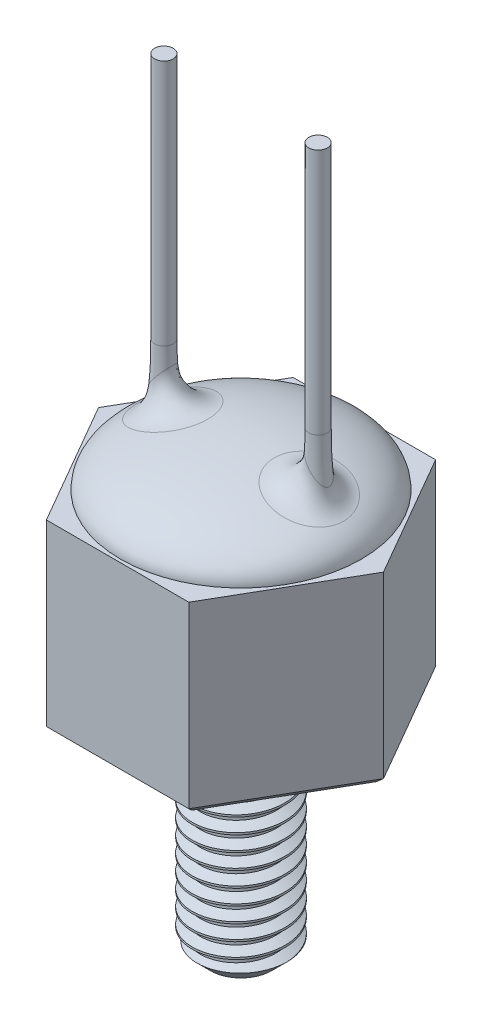
SolidWorks part; units mm, degrees
ref_plane "Спереди" through (0, 0, 0) normal (0, 0, 1) x (1, 0, 0)
ref_plane "Сверху" through (0, 0, 0) normal (0, 1, 0) x (1, 0, 0)
ref_plane "Справа" through (0, 0, 0) normal (1, 0, 0) x (0, 0, -1)
sketch "Эскиз1" plane through (0, 0, 0) normal (0, 1, 0) x (1, 0, 0)
  line L1 (4.6188, 0) -> (2.3094, 4)
  line L2 (2.3094, 4) -> (-2.3094, 4)
  line L3 (-2.3094, 4) -> (-4.6188, 0)
  line L4 (-4.6188, 0) -> (-2.3094, -4)
  line L5 (-2.3094, -4) -> (2.3094, -4)
  line L6 (2.3094, -4) -> (4.6188, 0)
  circle A0 centre (0, 0) radius 4 construction
extrude "Бобышка-Вытянуть1" add sketch "Эскиз1" along normal blind 6
sketch "Эскиз2" plane through (0, 0, 0) normal (0, -1, 0) x (1, 0, 0)
  circle A0 centre (0, 0) radius 1.6
sketch "Эскиз10" plane through (0, 0, 0) normal (0, 0, 1) x (1, 0, 0)
  line L0 (0, 0) -> (1.3, 0)
  line L1 (1.3, 0) -> (1.3, -0.5)
  line L2 (1.3, -0.5) -> (1.5, -0.5)
  line L3 (1.5, -0.5) -> (1.5, -6.5)
  line L4 (1, -7) -> (0, -7)
  line L5 (0, -7.4334) -> (0, 0.4467) construction
  line L6 (1.5, -6.5) -> (1, -7)
  line L7 (0, 0) -> (0, -7)
  point P5 (1.5, -7)
revolve "Повернуть1" add sketch "Эскиз10" angle 360 about L5
thread "Резьба2" pitch 0.5 method cut profile "Профиль резьбы2" start angle 0, offset 0, length 6.5, pitch 0.5, diameter 3
ref_plane "Плоскость5" through (1.5, -7, 0) normal (0, 0, 1) x (1, 0, 0)
sketch "Профиль резьбы2" plane through (1.5, -7, 0) normal (0, 0, 1) x (1, 0, 0)
  line L0 (0, 0) -> (0, 0.5) construction
  line L11 (0, 0) -> (0, 0.4375)
  line L12 (0, 0.4375) -> (-0.2706, 0.2812)
  line L13 (-0.2706, 0.2812) -> (-0.2706, 0.1562)
  line L15 (-0.2706, 0.1562) -> (0, 0)
  line L17 (-0.2706, 0.2187) -> (0, 0.2187) construction
  point P2 (0, 0)
  dimension "Pitch" = 0.5
  dimension "Profile_Angle" = 60
  dimension "Profile_Land" = 0.125
  dimension "Profile_Height" = 0.2706
sketch "Эскиз14" plane through (0, 0, 0) normal (0, 0, 1) x (1, 0, 0)
  line L0 (-2.3094, 6) -> (2.3094, 6) construction
  line L1 (0, 6) -> (3.9, 6)
  line L2 (2.3094, 6) -> (4.6188, 6) construction
  line L3 (0, 6) -> (0, 7.5)
  line L4 (0, 8.026) -> (0, 4.681) construction
  ellipse E0 centre (0, 6) end of major axis (-3.9, 6) minor radius 1.5 (3.9, 6) -> (0, 7.5) ccw
revolve "Повернуть2" add sketch "Эскиз14" angle 360 about L4
sketch "Эскиз15" plane through (0, 0, 0) normal (0, 0, 1) x (1, 0, 0)
  line L0 (2.5, 15) -> (2.5, 4) construction
  line L1 (2.5, 9) -> (2.1993, 9)
  line L2 (1.5, 6) -> (2.5, 6)
  line L3 (-2.3094, 6) -> (2.3094, 6) construction
  line L4 (2.5, 9) -> (2.5, 6)
  spline S0 degree 2 poles (2.1993, 9) (2.2058, 6.2322) (1.5, 6) knots 0 0 0 0.694246 0.694246 0.694246
revolve "Повернуть3" add sketch "Эскиз15" angle 360 about L0
mirror "Зеркальное отражение1" about plane through (0, 0, 0) normal (1, 0, 0) of "Повернуть3"
sketch "Эскиз16" plane through (0, 9, 0) normal (0, 1, 0) x (1, 0, 0)
  circle A0 centre (2.5, 0) radius 0.3
  circle A1 centre (-2.5, 0) radius 0.3
extrude "Бобышка-Вытянуть3" add sketch "Эскиз16" along normal blind 8
fillet "Скругление2" radius 1 2 edges at (-2.9357, 6.9868, -0.0957) (2.1119, 7.2605, -0.0923)
chamfer "Фаска1" distance 0.2 angle 45 6 edges at (-3.4641, 0, 2) (-3.4641, 0, -2) (0, 0, -4) (3.4641, 0, -2) (3.4641, 0, 2) (0, 0, 4)
